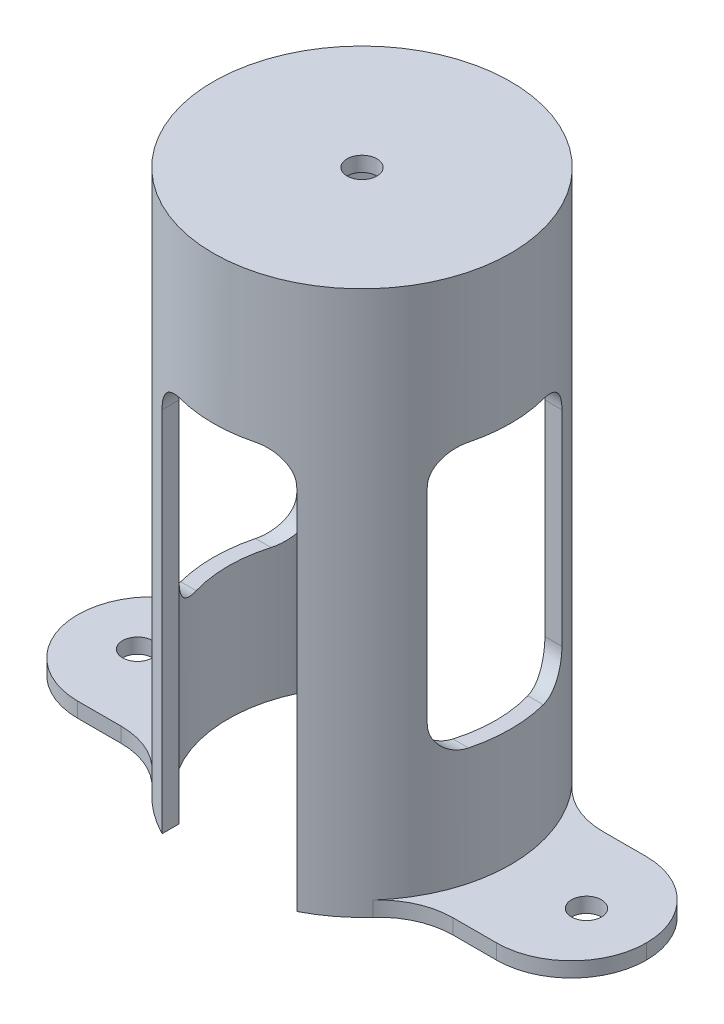
SolidWorks part; units mm, degrees
material "6061-T6 (SS)"
ref_plane "Front Plane" through (0, 0, 0) normal (0, 0, 1) x (1, 0, 0)
ref_plane "Top Plane" through (0, 0, 0) normal (0, 1, 0) x (1, 0, 0)
ref_plane "Right Plane" through (0, 0, 0) normal (1, 0, 0) x (0, 0, -1)
sketch "Sketch2" plane through (0, 0, 0) normal (0, 1, 0) x (1, 0, 0)
  circle A1 centre (0, 0) radius 9.9375
  dimension "D2" = 19.875
extrude "Boss-Extrude1" add sketch "Sketch2" along normal blind 35.384
sketch "Sketch4" plane through (0, 35.384, 0) normal (0, 1, 0) x (1, 0, 0)
  circle A0 centre (0, 0) radius 1
  dimension "D1" = 2
extrude "Cut-Extrude2" cut sketch "Sketch4" against normal through all
sketch "Sketch11" plane through (0, 0, 0) normal (0, -1, 0) x (1, 0, 0)
  line L0 (8.588, 5) -> (19, 5)
  line L1 (-19, 5) -> (-8.588, 5)
  line L2 (-19, 5) -> (-19, -5)
  line L3 (-19, -5) -> (-8.588, -5)
  line L4 (19, 5) -> (19, -5)
  line L5 (-19, 5) -> (19, -5) construction
  line L6 (-19, -5) -> (19, 5) construction
  line L7 (8.588, -5) -> (19, -5)
  arc A0 (8.588, 5) -> (-8.588, 5) centre (0, 0) ccw
  circle A1 centre (0, 0) radius 8.9375
  arc A2 (-8.588, -5) -> (8.588, -5) centre (0, 0) ccw
  point P0 (0, 0)
  dimension "D3" = 19.875
  dimension "D4" = 17.875
  dimension "D1" = 10
  dimension "D2" = 38
extrude "Boss-Extrude2" add sketch "Sketch11" along normal blind 1
sketch "Sketch12" plane through (0, 0, 0) normal (0, -1, 0) x (1, 0, 0)
  circle A0 centre (0, 0) radius 8.9375
  dimension "D1" = 17.875
extrude "Cut-Extrude7" cut sketch "Sketch12" against normal blind 34.384
ref_plane "Plane4" through (0, 0, 30) normal (0, 0, 1) x (1, 0, 0)
sketch "Sketch13" plane through (0, 0, 30) normal (0, 0, 1) x (1, 0, 0)
  line L0 (0, -10.9313) -> (0, 10.9313) construction
  line L1 (-4.5, 25.538) -> (4.5, 25.538)
  line L2 (-4.5, 25.538) -> (-4.5, -1)
  line L3 (-4.5, -1) -> (4.5, -1)
  line L4 (4.5, 25.538) -> (4.5, -1)
  line L5 (-4.5, 25.538) -> (4.5, -1) construction
  line L6 (-4.5, -1) -> (4.5, 25.538) construction
  line L7 (-8.588, -1) -> (8.588, -1) construction
  point P0 (0, 12.269)
  dimension "D1" = 26.538
  dimension "D2" = 9
extrude "Cut-Extrude8" cut sketch "Sketch13" against normal through all
ref_plane "Plane5" through (30, 0, 0) normal (1, 0, 0) x (0, 0, -1)
sketch "Sketch14" plane through (30, 0, 0) normal (1, 0, 0) x (0, 0, -1)
  line L0 (0, 10.9313) -> (0, -10.9313) construction
  line L1 (-4.5, 25.538) -> (4.5, 25.538)
  line L2 (-4.5, 25.538) -> (-4.5, 7.846)
  line L3 (-4.5, 7.846) -> (4.5, 7.846)
  line L4 (4.5, 25.538) -> (4.5, 7.846)
  line L5 (-4.5, 25.538) -> (4.5, 7.846) construction
  line L6 (-4.5, 7.846) -> (4.5, 25.538) construction
  line L7 (5, -1) -> (-5, -1) construction
  point P0 (0, 16.692)
  dimension "D2" = 9
  dimension "D1" = 17.692
  dimension "D3" = 17.692
extrude "Cut-Extrude9" cut sketch "Sketch14" against normal through all
fillet "Fillet3" radius 2 12 edges at (4.5, 25.538, -8.2911) (-4.5, 25.538, -8.2911) (-4.5, 25.538, 8.2911) (4.5, 25.538, 8.2911) (-8.2911, 25.538, 4.5) (-8.2911, 25.538, -4.5) (-8.2911, 7.846, -4.5) (-8.2911, 7.846, 4.5) (8.2911, 7.846, 4.5) (8.2911, 25.538, 4.5) (8.2911, 25.538, -4.5) (8.2911, 7.846, -4.5)
fillet "Fillet4" radius 5 8 edges at (8.588, -0.5, -5) (19, -0.5, -5) (8.588, -0.5, 5) (19, -0.5, 5) (-8.588, -0.5, 5) (-19, -0.5, -5) (-8.588, -0.5, -5) (-19, -0.5, 5)
sketch "Sketch15" plane through (0, 0, 0) normal (0, 1, 0) x (1, 0, 0)
  line L0 (-10.9313, 0) -> (10.9313, 0) construction
  circle A0 centre (-15, 0) radius 1
  circle A1 centre (15, 0) radius 1
  dimension "D1" = 15
  dimension "D2" = 15
extrude "Cut-Extrude10" cut sketch "Sketch15" against normal up to next
equation "\"FrangiboltTotalDiameter\"= 0.625in"
equation "\"FrangiboltTotalLength\"= 0.960in"
equation "\"FrangiboltThruHoleDiameter\"= 0.169in"
equation "\"EnclosureWallThickness\"= 1mm"
equation "\"EnclosureWallSpacing\"= 1mm"
equation "\"EnclosureInnerDiameter\"= \"FrangiboltTotalDiameter\" + 2 * \"EnclosureWallSpacing\""
equation "\"EnclosureOuterDiameter\"= \"FrangiboltTotalDiameter\" + 2 * \"EnclosureWallSpacing\" + 2 * \"EnclosureWallThickness\""
equation "\"EnclosureTotalLength\"= \"FrangiboltTotalLength\" + \"DamperLength\" + \"EnclosureWallThickness\""
equation "\"D2@Sketch2\"=\"EnclosureOuterDiameter\""
equation "\"D1@Boss-Extrude1\"=\"EnclosureTotalLength\""
equation "\"DamperLength\"= 10mm"
equation "\"EnclosureLip\"= 5mm"
equation "\"FrangiboltBoxWidth\"= 7mm"
equation "\"EnclosureMountingStandoff\"=38"
equation "\"D2@Sketch11\"=\"EnclosureMountingStandoff\""
equation "\"D3@Sketch11\"=\"EnclosureOuterDiameter\""
equation "\"D4@Sketch11\"=\"EnclosureInnerDiameter\""
equation "\"D1@Boss-Extrude2\"=\"EnclosureWallThickness\""
equation "\"D1@Sketch12\"=\"EnclosureInnerDiameter\""
equation "\"D1@Cut-Extrude7\"=\"EnclosureTotalLength\"-\"EnclosureWallThickness\""
equation "\"D1@Sketch13\"=\"EnclosureTotalLength\"*0.75"
equation "\"D2@Sketch13\"=\"FrangiboltBoxWidth\"+2mm"
equation "\"D1@Sketch14\"=\"EnclosureTotalLength\"*0.5"
equation "\"D2@Sketch14\"=\"FrangiboltBoxWidth\"+2mm"
equation "\"D3@Sketch14\"=\"EnclosureTotalLength\"*0.5"
equation "\"EnclosureMountingHoleDiameter\"= 2"
equation "\"D3@Sketch15\"=\"EnclosureMountingHoleDiameter\""
equation "\"D4@Sketch15\"=\"EnclosureMountingHoleDiameter\""
